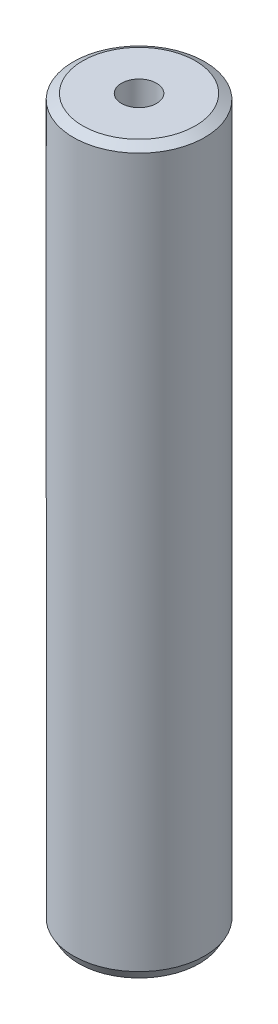
SolidWorks part; units mm, degrees
ref_plane "Front Plane" through (0, 0, 0) normal (0, 0, 1) x (1, 0, 0)
ref_plane "Top Plane" through (0, 0, 0) normal (0, 1, 0) x (1, 0, 0)
ref_plane "Right Plane" through (0, 0, 0) normal (1, 0, 0) x (0, 0, -1)
sketch "Sketch1" plane through (0, 0, 0) normal (0, 1, 0) x (1, 0, 0)
  circle A0 centre (0, 0) radius 10
  dimension "SHAFT_OD" = 20
extrude "Boss-Extrude1" add sketch "Sketch1" along normal blind 110.1689
sketch "Sketch2" plane through (0, 0, 0) normal (0, 1, 0) x (1, 0, 0)
  circle A0 centre (0, 0) radius 2.6719
  dimension "BORE_D" = 5.3439
extrude "Cut-Extrude1" cut sketch "Sketch2" along normal through all
chamfer "Chamfer1" distance 0.8217 angle 60 2 edges at (0, 110.1689, 10) (0, 0, 10) first distance on face at (0, 110.1689, 10) first distance on face at (0, 0, 2.6719)
